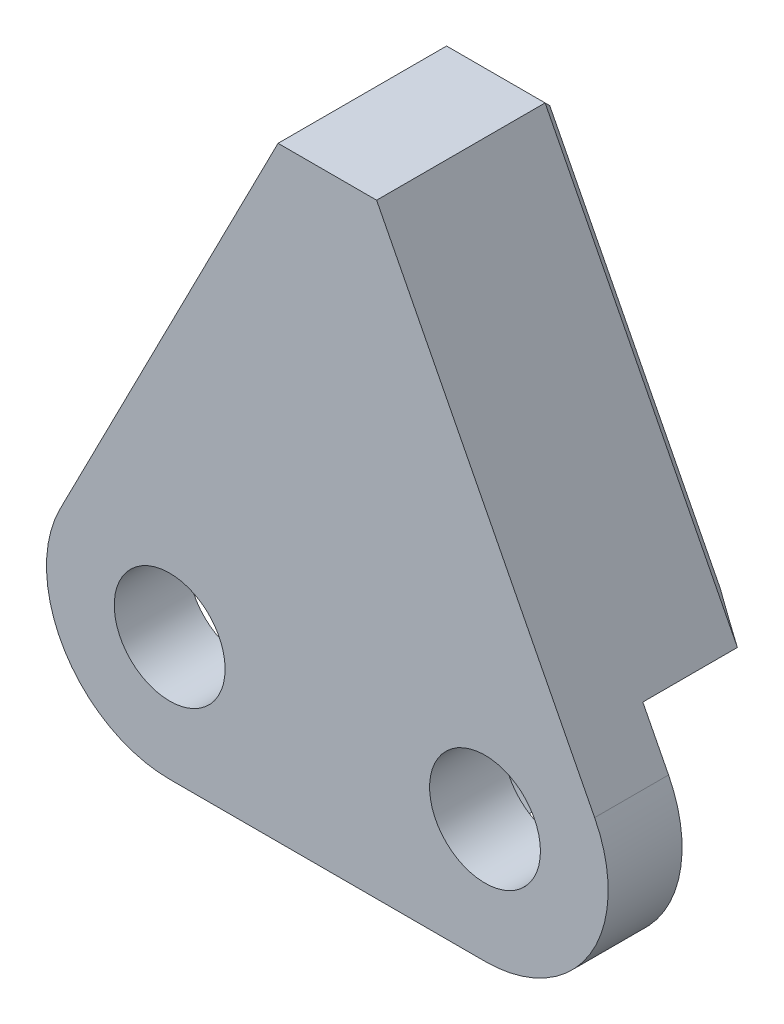
SolidWorks part; units mm, degrees
material "PET"
ref_plane "Front Plane" through (0, 0, 0) normal (0, 0, 1) x (1, 0, 0)
ref_plane "Top Plane" through (0, 0, 0) normal (0, 1, 0) x (1, 0, 0)
ref_plane "Right Plane" through (0, 0, 0) normal (1, 0, 0) x (0, 0, -1)
sketch "Sketch1" plane through (0, 0, 0) normal (0, 0, 1) x (1, 0, 0)
  line L0 (10.16, 24.1544) -> (10.16, -24.1544) construction
  line L1 (28.2575, 24.1544) -> (-7.9375, 24.1544) construction
  line L2 (-7.9375, -24.1544) -> (28.2575, -24.1544) construction
  line L3 (0, -7.9375) -> (20.32, -7.9375)
  line L4 (13.335, 31.0505) -> (6.985, 31.0505)
  line L5 (13.335, 31.0505) -> (27.3848, 3.6183)
  line L7 (10.795, 28.5105) -> (9.525, 28.5105) construction
  line L14 (6.985, 31.0505) -> (-7.0648, 3.6183)
  circle A0 centre (0, 0) radius 7.9375 construction
  arc A1 (27.3848, 3.6183) -> (20.32, -7.9375) centre (20.32, 0) cw
  circle A2 centre (0, 0) radius 7.9375
  arc A3 (-7.0648, 3.6183) -> (0, -7.9375) centre (0, 0) ccw
  point P10 (10.16, -7.9375)
  point P22 (10.16, 31.0505)
  dimension "D2" = 2.54
  dimension "D3" = 3.175
  dimension "D1" = 0
extrude "Boss-Extrude1" add sketch "Sketch1" along normal blind 4.7625
hole_wizard "1/4 Clearance Hole1" positions "Sketch4" profile "Sketch5" hole size "1/4" standard "ANSI Inch" end condition through all
sketch "Sketch4" plane through (0, 0, 4.7625) normal (0, 0, 1) x (1, 0, 0)
  circle A0 centre (0, 0) radius 3.5712 construction
  circle A1 centre (20.32, 0) radius 3.5712 construction
  point P0 (0, 0)
  point P2 (20.32, 0)
sketch "Sketch5" plane through (0, 0, 4.7625) normal (1, 0, 0) x (0, -1, 0)
  line L0 (0, 0) -> (0, 4.7625)
  line L1 (0, 4.7625) -> (3.5712, 4.7625)
  line L2 (3.5712, 4.7625) -> (3.5712, 0)
  line L5 (3.5712, 0) -> (0, 0)
  line L11 (0, -6.35) -> (0, 107.95) construction
  dimension "Thru Hole Dia." = 7.1425
  dimension "Thru Hole Depth" = 4.7625
sketch "Sketch6" plane through (0, 0, 0) normal (0, 0, -1) x (-1, 0, 0)
  line L0 (-16.8669, 24.1544) -> (-3.4531, 24.1544)
  line L1 (-28.2575, 24.1544) -> (7.9375, 24.1544) construction
  line L4 (7.0648, 3.6183) -> (-6.985, 31.0505)
  line L5 (-6.985, 31.0505) -> (-13.335, 31.0505)
  line L6 (-13.335, 31.0505) -> (-27.3848, 3.6183)
  line L7 (-20.32, -7.9375) -> (0, -7.9375)
  line L8 (-3.4531, 24.1544) -> (-6.985, 31.0505)
  line L9 (-6.985, 31.0505) -> (-13.335, 31.0505)
  line L10 (-13.335, 31.0505) -> (-16.8669, 24.1544)
  arc A2 (0, -7.9375) -> (7.0648, 3.6183) centre (0, 0) ccw
  arc A3 (-27.3848, 3.6183) -> (-20.32, -7.9375) centre (-20.32, 0) ccw
  dimension "D1" = 0
extrude "Boss-Extrude2" add sketch "Sketch6" along normal blind 6.858
draft "Draft1" type of draft neutral plane draft angle 30 faces to draft 1 face at (10.16, 24.1544, -3.429) neutral plane through (0, 0, -6.858) neutral plane normal (0, 0, -1) parameters "D1"=30
fillet "Fillet1" radius 12.7 1 edges at (10.16, 20.195, 0)
sketch "Sketch7" plane through (0, 0, 0) normal (0, 0, -1) x (-1, 0, 0)
  line L0 (-16.8669, 24.1544) -> (-3.4531, 24.1544)
  line L4 (7.0648, 3.6183) -> (2.3302, 12.8626)
  line L5 (2.3302, 12.8626) -> (-22.6502, 12.8626)
  line L6 (-22.6502, 12.8626) -> (-27.3848, 3.6183)
  line L7 (-20.32, -7.9375) -> (0, -7.9375)
  line L8 (5.4067, 6.8558) -> (2.3302, 12.8626)
  line L10 (-22.6502, 12.8626) -> (-25.7267, 6.8558)
  line L11 (-16.6826, -7.9375) -> (-3.6374, -7.9375)
  line L12 (-17.0172, 23.8611) -> (-22.6502, 12.8626)
  line L13 (-22.6502, 12.8626) -> (2.3302, 12.8626)
  line L14 (2.3302, 12.8626) -> (-3.3028, 23.8611)
  line L15 (-3.3028, 23.8611) -> (-17.0172, 23.8611)
  line L16 (-16.8669, 24.1544) -> (-22.6502, 12.8626)
  line L18 (2.3302, 12.8626) -> (-3.4531, 24.1544)
  arc A0 (5.4067, 6.8558) -> (-3.6374, -7.9375) centre (0, 0) ccw
  arc A1 (-16.6826, -7.9375) -> (-25.7267, 6.8558) centre (-20.32, 0) ccw
  arc A4 (-27.3848, 3.6183) -> (-20.32, -7.9375) centre (-20.32, 0) ccw
  arc A5 (0, -7.9375) -> (7.0648, 3.6183) centre (0, 0) ccw
  dimension "D1" = 17.4625
  dimension "D2" = 0
  dimension "D3" = 0
extrude "Boss-Extrude3" add sketch "Sketch7" along normal up to surface (6.858 mm away) up to face at (10.16, 27.6025, -6.858)
chamfer "Chamfer2" distance 3.175 angle 45 1 edges at (3.6374, -7.9375, -3.429) first distance on face at (10.16, -7.9375, -0.5239)
chamfer "Chamfer3" distance 3.175 angle 45 1 edges at (16.6826, -7.9375, -3.429) first distance on face at (10.9537, -7.9375, -0.5239)
chamfer "Chamfer1" distance 0.762 angle 45 8 edges at (10.16, 31.0505, -6.858) (0.7892, 18.9532, -6.858) (6.7839, 5.4967, -6.858) (10.16, -7.9375, -6.858) (13.5361, 5.4967, -6.858) (19.5308, 18.9532, -6.858) (6.1991, -7.3241, -6.858) (14.1209, -7.3241, -6.858)
